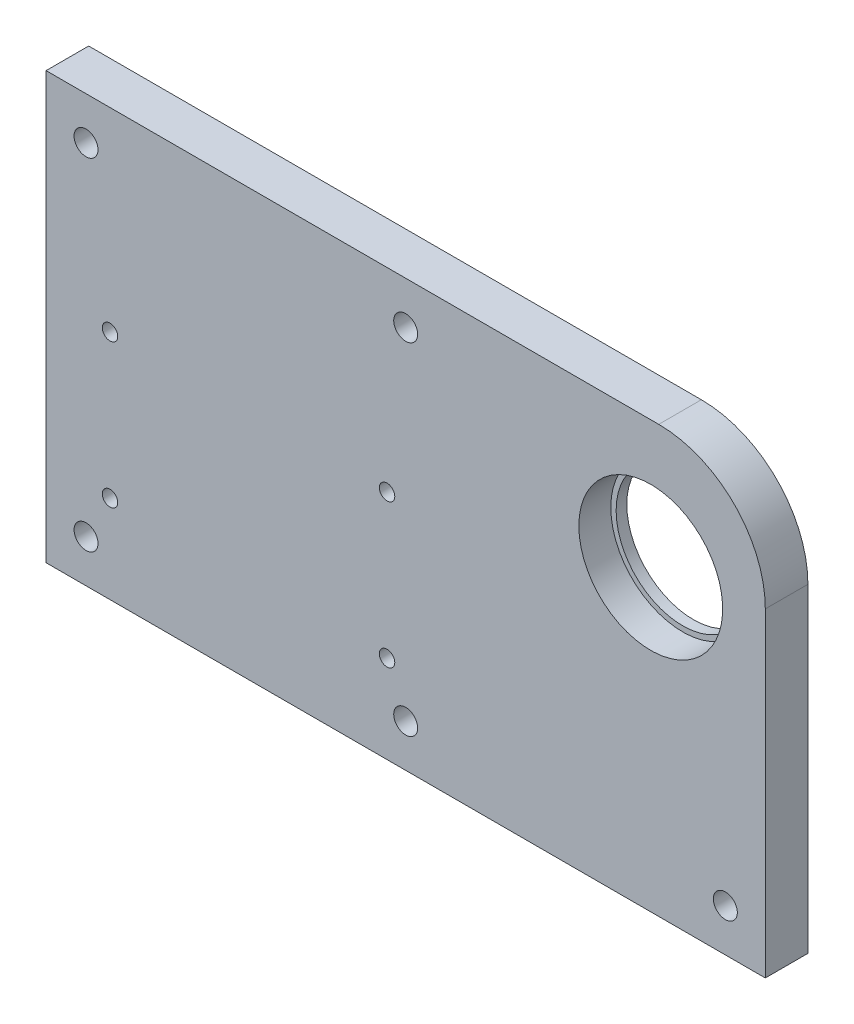
SolidWorks part; units mm, degrees
ref_plane "Front Plane" through (0, 0, 0) normal (0, 0, 1) x (1, 0, 0)
ref_plane "Top Plane" through (0, 0, 0) normal (0, 1, 0) x (1, 0, 0)
ref_plane "Right Plane" through (0, 0, 0) normal (1, 0, 0) x (0, 0, -1)
sketch "Sketch1" plane through (0, 0, 0) normal (0, 0, 1) x (1, 0, 0)
  line L0 (0, -35.0959) -> (0, 60.0008) construction
  line L1 (-88.188, 0) -> (125.974, 0) construction
  line L2 (14, 60.0008) -> (14, -35.0959) construction
  line L3 (-53.5, 50) -> (81.5, 50)
  line L4 (-53.5, 50) -> (-53.5, -30)
  line L5 (-53.5, -30) -> (81.5, -30)
  line L6 (81.5, 50) -> (81.5, -30)
  line L7 (60, 60.0008) -> (60, -35.0959) construction
  line L8 (-15.5, 17.2062) -> (-15.5, -16.829) construction
  line L9 (-41.5, 13.5) -> (10.5, 13.5) construction
  line L10 (-41.5, 13.5) -> (-41.5, -13.5) construction
  line L11 (-41.5, -13.5) -> (10.5, -13.5) construction
  line L12 (10.5, 13.5) -> (10.5, -13.5) construction
  line L13 (-88.188, 10) -> (125.974, 10) construction
  line L14 (31.1398, 26) -> (94.6254, 26) construction
  line L15 (-46, 10) -> (74, 10) construction
  line L16 (-46, 42) -> (74, 42) construction
  line L17 (-46, 42) -> (-46, -22) construction
  line L18 (-46, -22) -> (74, -22) construction
  line L19 (74, 42) -> (74, -22) construction
  point P20 (60, 26)
  point P24 (14, -22)
  point P25 (-46, -22)
  point P26 (74, -22)
  point P30 (-46, 10)
  point P32 (-46, 42)
  point P33 (14, 42)
  dimension "D1" = 135
  dimension "D2" = 80
  dimension "D3" = 67.5
  dimension "D4" = 14
  dimension "D6" = 60
  dimension "D7" = 52
  dimension "D9" = 27
  dimension "D10" = 13.5
  dimension "D8" = 26
  dimension "D11" = 15.5
  dimension "D12" = 10.5
  dimension "D5" = 10
  dimension "D13" = 40
  dimension "D14" = 16
  dimension "D15" = 46
  dimension "D18" = 64
  dimension "D19" = 120
  dimension "D20" = 0
  dimension "D21" = 60
  dimension "D22" = 60
  dimension "D16" = 3
  dimension "D17" = 2
extrude "Boss-Extrude1" add sketch "Sketch1" along normal blind 8
hole_wizard "CBORE for M2.5 SHCS1" positions "Sketch3" profile "Sketch4" counterbore size "M2.5" standard "ANSI Metric" end condition through all
sketch "Sketch3" plane through (0, 0, 0) normal (0, 0, -1) x (-1, 0, 0)
  point P0 (-10.5, 13.5)
  point P3 (-10.5, -13.5)
  point P6 (41.5, -13.5)
  point P9 (41.5, 13.5)
sketch "Sketch4" plane through (10.5, 13.5, 0) normal (1, 0, 0) x (0, 1, 0)
  line L0 (0, 0) -> (0, 8)
  line L1 (0, 8) -> (1.45, 8)
  line L3 (1.45, 8) -> (1.45, 2.5)
  line L4 (2.75, 2.5) -> (1.45, 2.5)
  line L5 (2.75, 2.5) -> (2.75, 0.025)
  line L6 (2.75, 0.025) -> (2.775, 0)
  line L7 (2.775, 0) -> (0, 0)
  line L8 (-2.75, 0.025) -> (-2.775, 0) construction
  line L11 (0, -6.35) -> (0, 107.95) construction
  dimension "Thru Hole Dia." = 2.9
  dimension "Thru Hole Depth" = 8
  dimension "C'Bore Dia." = 5.5
  dimension "C'Bore Depth" = 2.5
  dimension "Near C'Sink Dia." = 5.55
  dimension "Near C'Sink Angle" = 90
ref_axis "Axis1" through (0, 0, 0) along (0, 0, 1)
ref_axis "Axis2" through (60, 26, 0) along (0, 0, 1)
ref_plane "Plane2" through (60, 0, 0) normal (1, 0, 0) x (0, 0, -1)
sketch "Sketch5" plane through (60, 0, 0) normal (1, 0, 0) x (0, 0, -1)
  line L0 (-8, 39.5) -> (-2, 39.5)
  line L1 (-29.7967, 0) -> (24.2104, 0) construction
  line L2 (-2, 39.5) -> (-2, 38.5)
  line L3 (-2, 38.5) -> (0, 38.5)
  line L4 (0, 38.5) -> (0, 26)
  line L5 (0, 26) -> (-8, 26)
  line L6 (-8, 26) -> (-8, 39.5)
  line L7 (0, 42.1889) -> (0, 13.1062) construction
  line L8 (0, 26) -> (-15.4747, 26) construction
  dimension "D1" = 8
  dimension "D2" = 6
  dimension "D3" = 13.5
  dimension "D4" = 12.5
revolve "Cut-Revolve1" cut sketch "Sketch5" angle 360 about axis through (60, 26, 0) along (0, 0, 1)
hole_wizard "CBORE for M4 SHCS3" positions "Sketch16" profile "Sketch17" counterbore size "M4" standard "ANSI Metric" end condition through all
sketch "Sketch16" plane through (0, 0, 0) normal (0, 0, -1) x (-1, 0, 0)
  point P0 (46, -22)
  point P3 (-14, -22)
  point P6 (-74, -22)
  point P9 (46, 42)
  point P12 (-14, 42)
sketch "Sketch17" plane through (-46, -22, 0) normal (1, 0, 0) x (0, 1, 0)
  line L0 (0, 0) -> (0, 8)
  line L1 (0, 8) -> (2.25, 8)
  line L3 (2.25, 8) -> (2.25, 4)
  line L4 (4, 4) -> (2.25, 4)
  line L5 (4, 4) -> (4, 0.025)
  line L6 (4, 0.025) -> (4.025, 0)
  line L7 (4.025, 0) -> (0, 0)
  line L8 (-4, 0.025) -> (-4.025, 0) construction
  line L11 (0, -6.35) -> (0, 107.95) construction
  dimension "Thru Hole Dia." = 4.5
  dimension "Thru Hole Depth" = 8
  dimension "C'Bore Dia." = 8
  dimension "C'Bore Depth" = 4
  dimension "Near C'Sink Dia." = 8.05
  dimension "Near C'Sink Angle" = 90
fillet "Fillet1" radius 20 1 edges at (81.5, 50, 4)
equation "\"plateB_length\"= 135"
equation "\"D1@Sketch1\"=\"plateB_length\""
equation "\"plateB_height\"= 80"
equation "\"D2@Sketch1\"=\"plateB_height\""
equation "\"D3@Sketch1\"=\"plateB_length\"/2"
equation "\"motor_shaftA_center_center\"= 60"
equation "\"plateB_offsetX\"= 14"
equation "\"D4@Sketch1\"=\"plateB_offsetX\""
equation "\"D6@Sketch1\"=\"motor_shaftA_center_center\""
equation "\"plateB_thickness\"= 8"
equation "\"D1@Boss-Extrude1\"=\"plateB_thickness\""
equation "\"plateB_odB\"=25"
equation "\"plateB_odC\"=25"
equation "\"plateB_bearing_depth\"=6"
equation "\"motor_bolt_pattern_length\"=52"
equation "\"D7@Sketch1\"=\"motor_bolt_pattern_length\""
equation "\"motor_bolt_pattern_height\"=27"
equation "\"D9@Sketch1\"=\"motor_bolt_pattern_height\""
equation "\"D10@Sketch1\"=\"motor_bolt_pattern_height\"/2"
equation "\"D8@Sketch1\"=\"motor_bolt_pattern_length\"/2"
equation "\"motor_bolt_pattern_offsetX\"=15.5"
equation "\"D11@Sketch1\"=\"motor_bolt_pattern_offsetX\""
equation "\"plateB_offsetY\"=10"
equation "\"D5@Sketch1\"=\"plateB_offsetY\""
equation "\"D13@Sketch1\"=\"plateB_height\"/2"
equation "\"plateB_shaftA_offsetY\"=16"
equation "\"D14@Sketch1\"=\"plateB_shaftA_offsetY\""
equation "\"D1@Sketch5\"=\"plateB_thickness\""
equation "\"plateB_shaftA_bearing_depth\"=6"
equation "\"D2@Sketch5\"=\"plateB_shaftA_bearing_depth\""
equation "\"plateB_idC\"=27"
equation "\"D3@Sketch5\"=\"plateB_idC\"/2"
equation "\"plateB_idB\"=27"
equation "\"plateB_idA\"=25"
equation "\"D4@Sketch5\"=\"plateB_odB\"/2"
equation "\"plateB_bolt_pattern_height\"=64"
equation "\"D18@Sketch1\"=\"plateB_bolt_pattern_height\""
equation "\"plateB_bolt_pattern_length\"=120"
equation "\"D19@Sketch1\"=\"plateB_bolt_pattern_length\""
equation "\"plateB_bolt_pattern_offsetY\"=0"
equation "\"D20@Sketch1\"=\"plateB_bolt_pattern_offsetY\""
equation "\"plateB_bolt_spacingX\"= 60"
equation "\"D22@Sketch1\"=\"plateB_bolt_spacingX\""
equation "\"D21@Sketch1\"=\"plateB_bolt_spacingX\""
